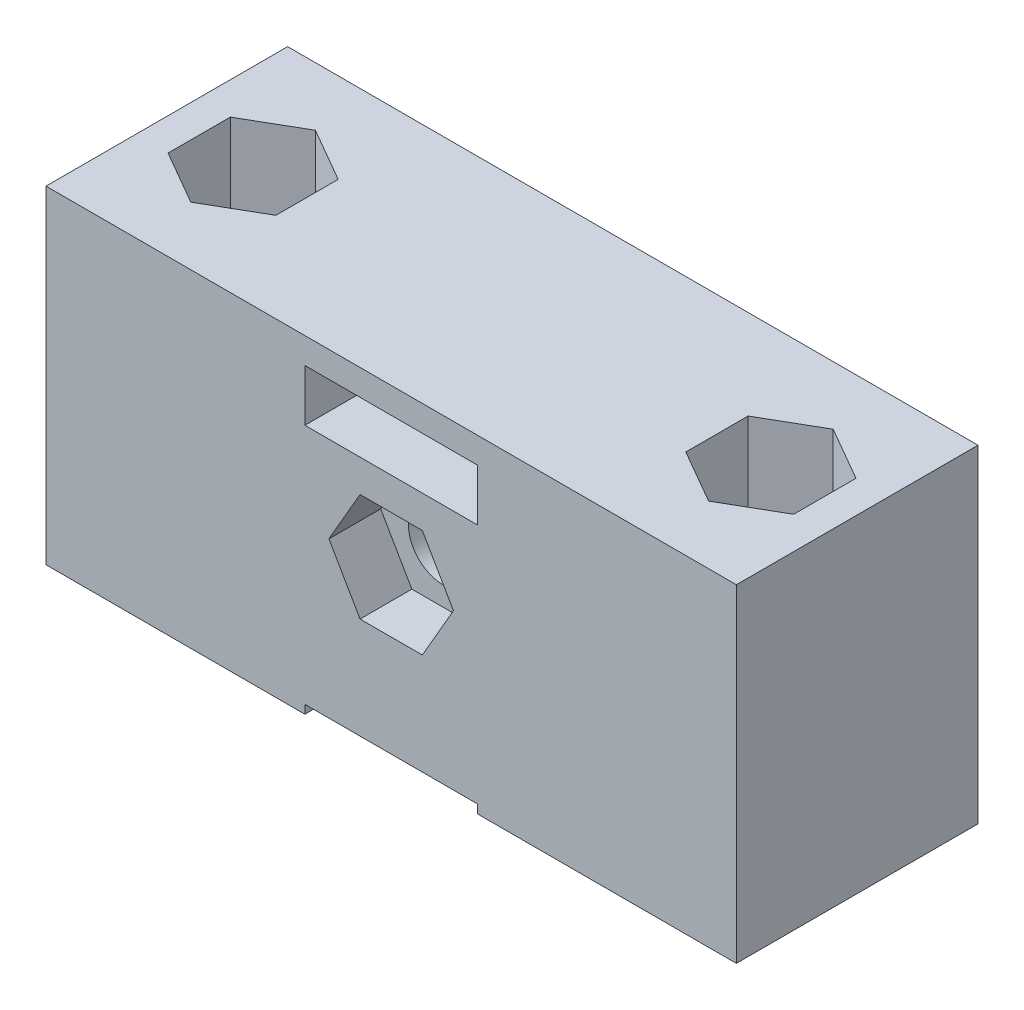
SolidWorks part; units mm, degrees
ref_plane "Front Plane" through (0, 0, 0) normal (0, 0, 1) x (1, 0, 0)
ref_plane "Top Plane" through (0, 0, 0) normal (0, 1, 0) x (1, 0, 0)
ref_plane "Right Plane" through (0, 0, 0) normal (1, 0, 0) x (0, 0, -1)
sketch "Sketch1" plane through (0, 0, 0) normal (0, 1, 0) x (1, 0, 0)
  line L1 (-20, 7) -> (20, 7)
  line L2 (-20, 7) -> (-20, -7)
  line L3 (-20, -7) -> (20, -7)
  line L4 (20, 7) -> (20, -7)
  line L5 (-20, 7) -> (20, -7) construction
  line L6 (-20, -7) -> (20, 7) construction
  point P0 (0, 0)
  dimension "D1" = 40
  dimension "D2" = 14
extrude "Boss-Extrude1" add sketch "Sketch1" along normal blind 19
sketch "Sketch2" plane through (0, 0, 7) normal (0, 0, 1) x (1, 0, 0)
  line L0 (0, 19) -> (0, 0) construction
  line L1 (-20, 19) -> (20, 19) construction
  line L3 (-5, 14.5) -> (5, 14.5)
  line L4 (-5, 14.5) -> (-5, 17.5)
  line L5 (-5, 17.5) -> (5, 17.5)
  line L6 (5, 14.5) -> (5, 17.5)
  line L7 (-5, 14.5) -> (5, 17.5) construction
  line L8 (-5, 17.5) -> (5, 14.5) construction
  line L9 (-5, -0.5) -> (5, -0.5)
  line L10 (-5, -0.5) -> (-5, 0.5)
  line L11 (-5, 0.5) -> (5, 0.5)
  line L12 (5, -0.5) -> (5, 0.5)
  line L13 (-5, -0.5) -> (5, 0.5) construction
  line L14 (-5, 0.5) -> (5, -0.5) construction
  point P5 (0, 16)
  dimension "D1" = 10
  dimension "D2" = 3
  dimension "D3" = 16
  dimension "D4" = 10
  dimension "D5" = 1
extrude "Cut-Extrude1" cut sketch "Sketch2" against normal blind 30
sketch "Sketch3" plane through (0, 0, 7) normal (0, 0, 1) x (1, 0, 0)
  line L0 (0, 19) -> (0, 0) construction
  line L1 (-20, 19) -> (20, 19) construction
  circle A0 centre (0, 9.5) radius 2
  dimension "D1" = 4
extrude "Cut-Extrude2" cut sketch "Sketch3" against normal through all
sketch "Sketch4" plane through (0, 19, 0) normal (0, 1, 0) x (1, 0, 0)
  line L0 (-20, 0) -> (20, 0) construction
  line L1 (-20, 7) -> (-20, -7) construction
  line L2 (20, -7) -> (20, 7) construction
  line L3 (0, 7) -> (0, -7) construction
  line L4 (20, 7) -> (-20, 7) construction
  line L5 (-20, -7) -> (20, -7) construction
  circle A0 centre (-15, 0) radius 1.6
  circle A1 centre (15, 0) radius 1.6
  dimension "D1" = 3.2
  dimension "D2" = 15
extrude "Cut-Extrude3" cut sketch "Sketch4" against normal through all
sketch "Sketch8" plane through (0, 0, 0) normal (0, -1, 0) x (-1, 0, 0)
  line L0 (-5, 7) -> (-5, -7) construction
  line L1 (5, -7) -> (-5, -7)
  line L2 (5, -7) -> (5, -6)
  line L3 (5, -6) -> (-5, -6)
  line L4 (-5, -7) -> (-5, -6)
  dimension "D1" = 1
extrude "Boss-Extrude2" [suppressed] add sketch "Sketch8" against normal up to next
sketch "Sketch9" plane through (0, 19, 0) normal (0, 1, 0) x (1, 0, 0)
  line L0 (0, 7) -> (0, -7) construction
  line L1 (-15, 3.6084) -> (-18.125, 1.8042)
  line L2 (-18.125, 1.8042) -> (-18.125, -1.8042)
  line L3 (-18.125, -1.8042) -> (-15, -3.6084)
  line L4 (-15, -3.6084) -> (-11.875, -1.8042)
  line L5 (-11.875, -1.8042) -> (-11.875, 1.8042)
  line L6 (-11.875, 1.8042) -> (-15, 3.6084)
  line L7 (20, 7) -> (-20, 7) construction
  line L8 (-20, -7) -> (20, -7) construction
  line L9 (11.875, 1.8042) -> (15, 3.6084)
  line L10 (11.875, -1.8042) -> (11.875, 1.8042)
  line L11 (15, -3.6084) -> (11.875, -1.8042)
  line L12 (18.125, -1.8042) -> (15, -3.6084)
  line L13 (18.125, 1.8042) -> (18.125, -1.8042)
  line L14 (15, 3.6084) -> (18.125, 1.8042)
  circle A0 centre (-15, 0) radius 3.125 construction
  circle A1 centre (15, 0) radius 3.125 construction
  dimension "D1" = 6.25
extrude "Cut-Extrude4" cut sketch "Sketch9" against normal blind 10
sketch "Sketch10" plane through (0, 0, 7) normal (0, 0, 1) x (1, 0, 0)
  line L1 (1.8042, 12.625) -> (-1.8042, 12.625)
  line L2 (-1.8042, 12.625) -> (-3.6084, 9.5)
  line L3 (-3.6084, 9.5) -> (-1.8042, 6.375)
  line L4 (-1.8042, 6.375) -> (1.8042, 6.375)
  line L5 (1.8042, 6.375) -> (3.6084, 9.5)
  line L6 (3.6084, 9.5) -> (1.8042, 12.625)
  circle A0 centre (0, 9.5) radius 3.125 construction
  dimension "D1" = 6.25
extrude "Cut-Extrude5" cut sketch "Sketch10" against normal blind 3
equation "\"X-ROD-SPACING\"=45"
equation "\"Y-ROD-SPACING\"=75"
equation "\"Z-ROD-SPACING\"=17.5"
equation "\"Y-BED-OFFSET\"=2"
equation "\"Y-BED-ROD-INSET\"=3.5"
equation "\"Y-BED-SCREW-SPACING\"=209"
equation "\"Y-BED-SCREW-CUTOUT-SLOT-HEIGHT\"=2"
equation "\"T-SLOT-NUT-FILLET-RADIUS\"=0.25"
equation "\"T-SLOT-SCREW-SHAFT-RADIUS\"=1.75"
equation "\"T-SLOT-SCREW-SHAFT-CUTOUT-LENGTH\"=10.5"
equation "\"T-SLOT-NUT-DEPTH\"=4.2"
equation "\"T-SLOT-NUT-WIDTH\"=3"
equation "\"T-SLOT-NUT-END-DISTANCE\"=8"
equation "\"ACRYLIC-THICKNESS\"=10"
equation "\"ACRYLIC-THICKNESS2\"=4.5"
equation "\"ACRYLIC-TAB-CUTOUT-SIZE\"=\"ACRYLIC-THICKNESS\"+\"ACRYLIC-TAB-TOLERANCE\"*2"
equation "\"ACRYLIC-TAB-TOLERANCE\"=.1"
equation "\"ACRYLIC-TAB-WIDTH\"=\"ACRYLIC-THICKNESS\""
equation "\"ACRYLIC-M3-HOLE\"=3.1"
equation "\"SMOOTHROD-CAP-SCREW-DISTANCE\"=20"
equation "\"FRAME-WIDTH-INNER\"=370"
equation "\"NEMA17-HOLE-SPACING\"=31"
equation "\"NEMA17-CENTRAL-CUTOUT\"=22.5"
equation "\"Z-BRACKET-REACH\"=55"
equation "\"Z-ROD-INSET\"=16"
equation "\"TOP-BRACKET-SPACING\"=40"
equation "\"SMOOTHROD-X-LENGTH\"=350"
equation "\"SMOOTHROD-Y-LENGTH\"=350"
equation "\"SMOOTHROD-Z-LENGTH\"=350"
equation "\"SMOOTHROD-TIGHTENING-HEADROOM\"=.25"
equation "\"LEADSCREW-Z-LENGTH\"=300"
equation "\"SCREW-LENGTH-FRAME\"=\"ACRYLIC-THICKNESS\" + 10"
equation "\"SCREW-LENGTH-MOTOR\"=\"ACRYLIC-THICKNESS\" + 5"
equation "\"SCREW-LENGTH-EXTRUDER\"=28"
equation "\"SCREW-HEAD-RADIUS\"=6"
equation "\"PRINTED-M3-HOLE\"=3.5"
equation "\"PRINTED-X-SMOOTHROD-DIAMETER\"=8.2"
equation "\"PRINTED-X-SMOOTHROD-CUTOUT\"=10"
equation "\"PRINTED-X-BASE-HEIGHT\"=10"
equation "\"PRINTED-LM8UU-CUTOUT-SIZE\"=15.25"
equation "\"PRINTED-LM8UU-CUTOUT-LENGTH\"=24.5"
equation "\"PRINTED-X-IDLER-HEIGHT\"=16"
equation "\"PSU-MOUNTING-WIDTH\"=95"
equation "\"PSU-MOUNTING-HEIGHT\"=177"
equation "\"Y-BELT-TO-ROD-DISTANCE\"=20"
equation "\"SPOOL-HOLDER-ROD-SPACING\"=150"
equation "\"ACRYLIC-X-CARRIAGE-WIDTH\"=55"
equation "\"ACRYLIC-X-CARRIAGE-HEIGHT\"=75"
equation "\"ACRYLIC-X-CARRIAGE-LM8UU-CUTOUT-WIDTH\"=24.25"
equation "\"ACRYLIC-X-CARRIAGE-LM8UU-CUTOUT-HEIGHT\"=11.5"
equation "\"ACRYLIC-X-CARRIAGE-SCREW-SPACING-X\"=15"
equation "\"ACRYLIC-X-CARRIAGE-SCREW-SPACING-Y\"=33"
equation "\"ACRYLIC-X-CARRIAGE-CENTER-TAB-SPACING\"=14"
equation "\"ACRYLIC-X-CARRIAGE-EXTRUDER-OFFSET\"=26"
equation "\"ACRYLIC-X-CARRIAGE-EXTRUDER-ANGLE\"=90"
equation "\"ACRYLIC-X-CARRIAGE-EXTRUDER-SHELF-DEPTH\"=\"ACRYLIC-X-CARRIAGE-EXTRUDER-OFFSET\" + 28"
equation "\"ACRYLIC-X-CARRIAGE-EXTRUDER-BRACE-SPACING\"=23"
equation "\"ACRYLIC-X-CARRIAGE-EXTRUDER-BRACE-TAB-OFFSET\"=20"
equation "\"ACRYLIC-X-CARRIAGE-EXTRUDER-BRACE-HEIGHT\"=35"
equation "\"ACRYLIC-X-CARRIAGE-EXTRUDER-BRACE-SCREW-SPACING\"=22"
equation "\"ACRYLIC-X-CARRIAGE-DUAL-WIDTH-MULTIPLIER\"=1.65"
equation "\"ACRYLIC-X-CARRIAGE-DUAL-HOTEND-SPACING\"=42"
equation "\"ACRYLIC-X-CARRIAGE-DUAL-WIDTH\"=75"
equation "\"ACRYLIC-X-CARRIAGE-DUAL-HOTEND-SEPARATION\"=36"
equation "\"ACRYLIC-X-CARRIAGE-DUAL-MOUNT-PLATE-DEPTH\"=75"
equation "\"ACRYLIC-X-CARRIAGE-DUAL-MOUNT-BRACE-WIDTH\"=33"
equation "\"ACRYLIC-X-CARRIAGE-DUAL-MOUNT-SCREW-WIDTH\"=40"
equation "\"BLOWER-FAN-WIDTH\"=15"
equation "\"PRINTED-M3-NUT-AF\"=6.25"
equation "\"D1@Sketch9\"=\"PRINTED-M3-NUT-AF\""
equation "\"D1@Sketch10\"=\"PRINTED-M3-NUT-AF\""
